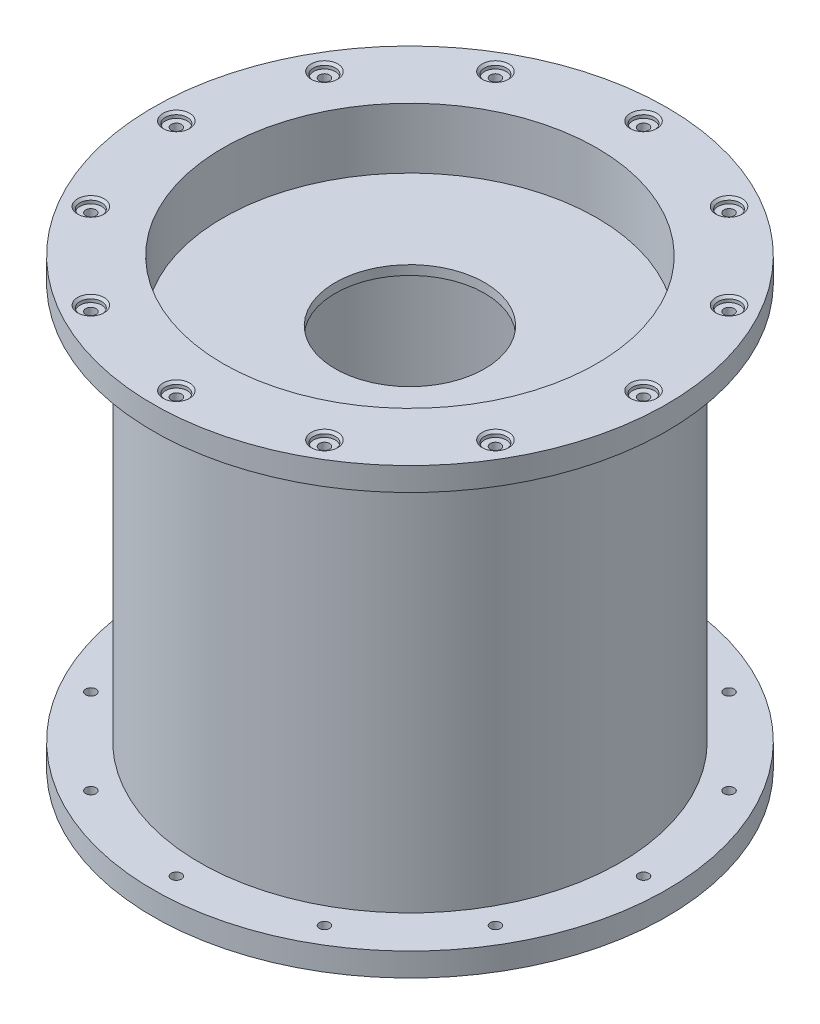
SolidWorks part; units mm, degrees
ref_plane "Front Plane" through (0, 0, 0) normal (0, 0, 1) x (1, 0, 0)
ref_plane "Top Plane" through (0, 0, 0) normal (0, 1, 0) x (1, 0, 0)
ref_plane "Right Plane" through (0, 0, 0) normal (1, 0, 0) x (0, 0, -1)
sketch "Sketch1" plane through (0, 0, 0) normal (1, 0, 0) x (0, 0, -1)
  line L1 (57.15, 6.35) -> (57.15, 114.3)
  line L8 (57.15, 120.65) -> (69.85, 120.65)
  line L9 (69.85, 120.65) -> (69.85, 114.3)
  line L10 (69.85, 114.3) -> (57.15, 114.3)
  line L11 (57.15, 0) -> (69.85, 0)
  line L12 (69.85, 0) -> (69.85, 6.35)
  line L13 (69.85, 6.35) -> (57.15, 6.35)
  line L27 (50.8, 114.3) -> (50.8, 120.65)
  line L28 (50.8, 120.65) -> (57.15, 120.65)
  line L29 (50.8, 6.35) -> (50.8, 0)
  line L30 (50.8, 0) -> (57.15, 0)
  line L31 (50.8, 114.3) -> (50.8, 6.35)
  line L32 (50.8, 0) -> (0, 0) construction
  line L33 (0, 0) -> (0, 6.35) construction
  dimension "D1" = 6.35
  dimension "D2" = 6.35
  dimension "D3" = 12.7
  dimension "D4" = 12.7
  dimension "D5" = 12.7
  dimension "D6" = 12.7
  dimension "D7" = 107.95
  dimension "D8" = 50.8
  dimension "D9" = 6.35
revolve "Chamber" add sketch "Sketch1" angle 360 about L33
sketch "Sketch4" plane through (0, 0, 0) normal (1, 0, 0) x (0, 0, -1)
  line L0 (0, 0) -> (0, 120.65) construction
  line L1 (50.8, 120.65) -> (-50.8, 120.65) construction
  line L3 (50.8, 104.2017) -> (20.32, 104.2017)
  line L7 (50.8, 104.2017) -> (50.8, 101.6617)
  line L8 (0, 60.325) -> (57.15, 60.325) construction
  line L9 (20.32, 104.2017) -> (20.32, 101.6617)
  line L10 (50.8, 16.4483) -> (20.32, 16.4483)
  line L11 (50.8, 16.4483) -> (50.8, 18.9883)
  line L12 (50.8, 18.9883) -> (20.32, 18.9883)
  line L13 (20.32, 16.4483) -> (20.32, 18.9883)
  line L14 (50.8, 101.6617) -> (20.32, 101.6617)
  point P9 (50.7813, 15.9134)
  point P10 (50.342, 18.9883)
  dimension "D1" = 2.54
  dimension "D2" = 30.48
revolve "Turbulence Rings" add sketch "Sketch4" angle 360 about L0
sketch "Sketch5" plane through (0, 120.65, 0) normal (0, 1, 0) x (1, 0, 0)
  line L0 (0, 0) -> (-63.5, 0) construction
  line L1 (0, 0) -> (-54.9926, 31.75) construction
  circle A0 centre (0, 0) radius 63.5 construction
  point P0 (0, 0)
  point P5 (-63.5, 0)
  point P9 (-54.9926, 31.75)
  point P10 (-31.75, 54.9926)
  point P11 (0, 63.5)
  point P12 (31.75, 54.9926)
  point P13 (54.9926, 31.75)
  point P14 (63.5, 0)
  point P15 (54.9926, -31.75)
  point P16 (31.75, -54.9926)
  point P17 (0, -63.5)
  point P18 (-31.75, -54.9926)
  point P19 (-54.9926, -31.75)
  point P20 (0, 0)
  dimension "D1" = 30
  dimension "D2" = 12
hole_wizard "CBORE for #3 Binding Head Machine Screw2" positions "Sketch5" profile "Sketch9" counterbore size "#3" standard "ANSI Inch" end condition through all
sketch "Sketch9" plane through (-54.9926, 120.65, 31.75) normal (1, 0, 0) x (0, 0, 1)
  line L0 (0, 0) -> (0, 120.65)
  line L1 (1.397, 118.4351) -> (3.6119, 120.65)
  line L2 (2.9769, 1.4986) -> (1.397, 1.4986)
  line L3 (1.397, 1.4986) -> (1.397, 118.4351)
  line L5 (2.9769, 1.4986) -> (2.9769, 0.635)
  line L6 (2.9769, 0.635) -> (3.6119, 0)
  line L7 (3.6119, 0) -> (0, 0)
  line L8 (-2.9769, 0.635) -> (-3.6119, 0) construction
  line L11 (0, -6.35) -> (0, 107.95) construction
  line L12 (3.6119, 120.65) -> (0, 120.65)
  line L13 (-1.397, 118.4351) -> (-3.6119, 120.65) construction
  dimension "Thru Hole Dia." = 2.794
  dimension "Thru Hole Depth" = 120.65
  dimension "C'Bore Dia." = 5.9538
  dimension "C'Bore Depth" = 1.4986
  dimension "Near C'Sink Dia." = 7.2238
  dimension "Near C'Sink Angle" = 90
  dimension "Far C'Sink Dia." = 7.2238
  dimension "Far C'Sink Angle" = 90
equation "\"Thickness of Material\"= 0.3in"
equation "\"Chamber Length\"= 4.25in"
equation "\"Flange Length\"= 0.5in"
equation "\"Chamber Wall Thickness\"= 0.25in"
equation "\"Ring Length\"= 1.2in"
equation "\"Ring Thickness\"= 0.1in"
equation "\"Number of Rings\" = 2"
equation "\"Chamber Radius\"= 2in"
